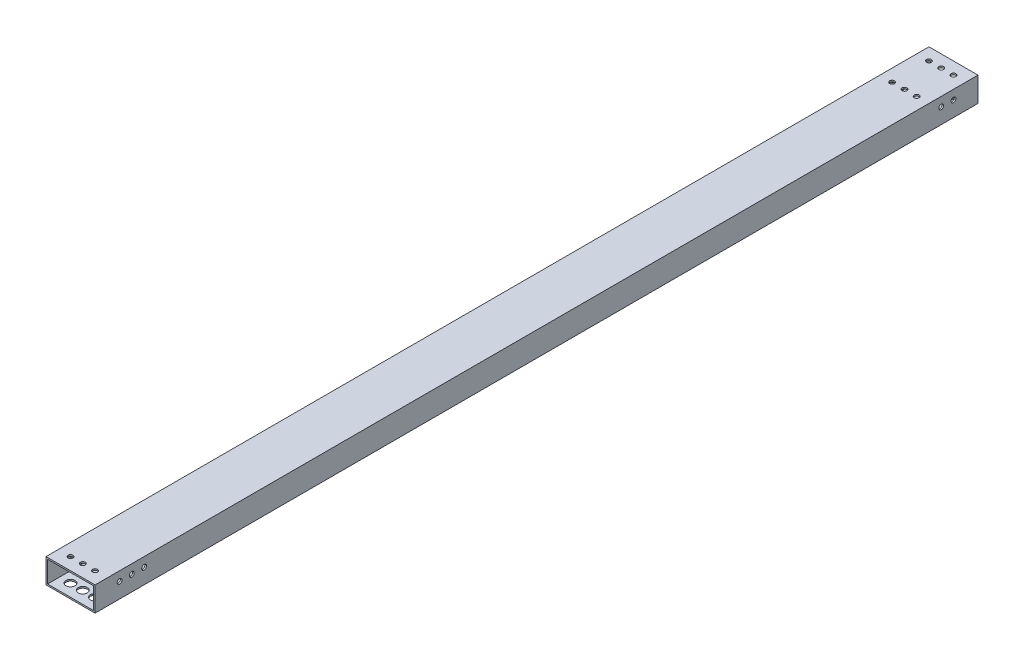
SolidWorks part; units mm, degrees
other "Markup1"
sketch "Sketch5" plane through (-25.4, -12.7, -457.2) normal (-0.35, -0.9329, -0.0852) x (-0.8023, 0.2515, 0.5413)
sketch "Sketch6" plane through (-25.4, -12.7, -457.2) normal (-0.35, -0.9329, -0.0852) x (-0.8023, 0.2515, 0.5413)
sketch "Sketch8" plane through (-25.4, -12.7, -457.2) normal (-0.35, -0.9329, -0.0852) x (-0.8023, 0.2515, 0.5413)
sketch "Sketch9" plane through (-25.4, -12.7, -457.2) normal (-0.35, -0.9329, -0.0852) x (-0.8023, 0.2515, 0.5413)
sketch "Sketch11" plane through (-25.4, -12.7, -457.2) normal (-0.35, -0.9329, -0.0852) x (-0.8023, 0.2515, 0.5413)
sketch "Sketch13" plane through (-25.4, -12.7, -457.2) normal (-0.35, -0.9329, -0.0852) x (-0.8023, 0.2515, 0.5413)
sketch "Sketch14" plane through (-25.4, -12.7, -457.2) normal (-0.35, -0.9329, -0.0852) x (-0.8023, 0.2515, 0.5413)
material "6061-T6 (SS)"
ref_plane "Front Plane" through (0, 0, 0) normal (0, 0, 1) x (1, 0, 0)
ref_plane "Top Plane" through (0, 0, 0) normal (0, 1, 0) x (1, 0, 0)
ref_plane "Right Plane" through (0, 0, 0) normal (1, 0, 0) x (0, 0, -1)
sketch "Sketch1" plane through (0, 0, 0) normal (0, 0, 1) x (1, 0, 0)
  line L0 (-23.8125, 11.1125) -> (23.8125, 11.1125)
  line L1 (-25.4, -12.7) -> (25.4, -12.7)
  line L2 (-25.4, -12.7) -> (-25.4, 12.7)
  line L3 (-25.4, 12.7) -> (25.4, 12.7)
  line L4 (25.4, -12.7) -> (25.4, 12.7)
  line L5 (-25.4, -12.7) -> (25.4, 12.7) construction
  line L6 (-25.4, 12.7) -> (25.4, -12.7) construction
  line L7 (23.8125, -11.1125) -> (23.8125, 11.1125)
  line L8 (-23.8125, -11.1125) -> (23.8125, -11.1125)
  line L9 (-23.8125, -11.1125) -> (-23.8125, 11.1125)
  point P0 (0, 0)
  dimension "D1" = 50.8
  dimension "D2" = 25.4
  dimension "D3" = 1.5875
extrude "Boss-Extrude1" add sketch "Sketch1" along normal mid plane 914.4
sketch "Sketch3" plane through (0, 12.7, 0) normal (0, 1, 0) x (1, 0, 0)
  line L2 (25.4, -457.2) -> (-25.4, -457.2) construction
  line L3 (25.4, 0) -> (-25.4, 0) construction
  line L4 (25.4, -457.2) -> (25.4, 457.2) construction
  line L5 (-25.4, -457.2) -> (-25.4, 457.2) construction
  circle A0 centre (0, -444.5) radius 2.5527
  circle A1 centre (12.7, -444.5) radius 2.5527
  circle A2 centre (-12.7, -444.5) radius 2.5527
  circle A3 centre (12.7, 444.5) radius 2.5527
  circle A4 centre (0, 444.5) radius 2.5527
  circle A5 centre (-12.7, 444.5) radius 2.5527
  dimension "D1" = 5.1054
  dimension "D2" = 12.7
  dimension "D3" = 12.7
  dimension "D4" = 12.7
extrude "Cut-Extrude2" cut sketch "Sketch3" against normal up to surface (1.5875 mm away) up to face at (0, 11.1125, 0)
sketch "Sketch4" plane through (0, -12.7, 0) normal (0, -1, 0) x (1, 0, 0)
  circle A0 centre (-12.7, 444.5) radius 2.5527 construction
  circle A1 centre (0, 444.5) radius 2.5527 construction
  circle A2 centre (12.7, 444.5) radius 2.5527 construction
  circle A3 centre (-12.7, 444.5) radius 2.5527
  circle A4 centre (0, 444.5) radius 2.5527
  circle A5 centre (12.7, 444.5) radius 2.5527
  circle A6 centre (-12.7, -444.5) radius 2.5527 construction
  circle A7 centre (0, -444.5) radius 2.5527 construction
  circle A8 centre (12.7, -444.5) radius 2.5527 construction
  circle A9 centre (-12.7, -444.5) radius 2.5527
  circle A10 centre (0, -444.5) radius 2.5527
  circle A11 centre (12.7, -444.5) radius 2.5527
  circle A12 centre (-12.7, 444.5) radius 4.7625
  circle A13 centre (0, 444.5) radius 4.7625
  circle A14 centre (12.7, 444.5) radius 4.7625
  circle A15 centre (-12.7, -444.5) radius 4.7625
  circle A16 centre (0, -444.5) radius 4.7625
  circle A17 centre (12.7, -444.5) radius 4.7625
  dimension "D1" = 9.525
  dimension "D2" = 9.525
extrude "Cut-Extrude4" cut sketch "Sketch4" against normal up to surface (1.5875 mm away) contours A12 A3 | A13 A4 | A4 | A3 | A5 | A14 A5 | A11 | A17 A11 | A16 A10 | A10 | A15 A9 | A9 region at (-12.7, -12.7, 444.5) region at (0, -12.7, 444.5) region at (12.7, -12.7, 444.5) region at (-12.7, -12.7, -444.5) region at (0, -12.7, -444.5) region at (12.7, -12.7, -444.5) region at (-17.3278, -12.7, 444.5) region at (-4.6278, -12.7, 444.5) region at (8.0722, -12.7, 444.5) region at (-17.3278, -12.7, -444.5) region at (-4.6278, -12.7, -444.5) region at (8.0722, -12.7, -444.5) up to face at (0, -11.1125, 0)
sketch "Sketch7" plane through (25.4, 0, 0) normal (1, 0, 0) x (0, 0, -1)
  line L0 (-457.2, -12.7) -> (-457.2, 12.7) construction
  line L1 (-457.2, 12.7) -> (457.2, 12.7) construction
  line L2 (0, 12.7) -> (0, -12.7) construction
  line L3 (-457.2, -12.7) -> (457.2, -12.7) construction
  circle A0 centre (-444.5, 3.175) radius 2.4892
  circle A1 centre (-431.8, 3.175) radius 2.4892
  circle A2 centre (-419.1, 3.175) radius 2.4892
  circle A3 centre (-406.4, 3.175) radius 2.4892
  circle A4 centre (406.4, 3.175) radius 2.4892
  circle A5 centre (419.1, 3.175) radius 2.4892
  circle A6 centre (431.8, 3.175) radius 2.4892
  circle A7 centre (444.5, 3.175) radius 2.4892
  dimension "D3" = 4.9784
  dimension "D1" = 12.7
  dimension "D2" = 9.525
  dimension "D4" = 12.7
  dimension "D5" = 12.7
  dimension "D6" = 12.7
extrude "Cut-Extrude5" cut sketch "Sketch7" against normal through all contours A5 | A6 | A1 | A2 | A3 region at (25.4, 3.175, 431.8) region at (25.4, 3.175, 419.1) region at (25.4, 3.175, 406.4) region at (25.4, 3.175, -419.1) region at (25.4, 3.175, -431.8)
sketch "Sketch10" plane through (0, 12.7, 0) normal (0, 1, 0) x (1, 0, 0)
  line L0 (25.4, 457.2) -> (-25.4, 457.2) construction
  circle A0 centre (-12.7, 406.4) radius 2.5527
  circle A1 centre (0, 406.4) radius 2.5527
  circle A2 centre (12.7, 406.4) radius 2.5527
  dimension "D1" = 5.1054
  dimension "D2" = 12.7
  dimension "D3" = 12.7
  dimension "D4" = 50.8
extrude "Cut-Extrude6" cut sketch "Sketch10" against normal through all
